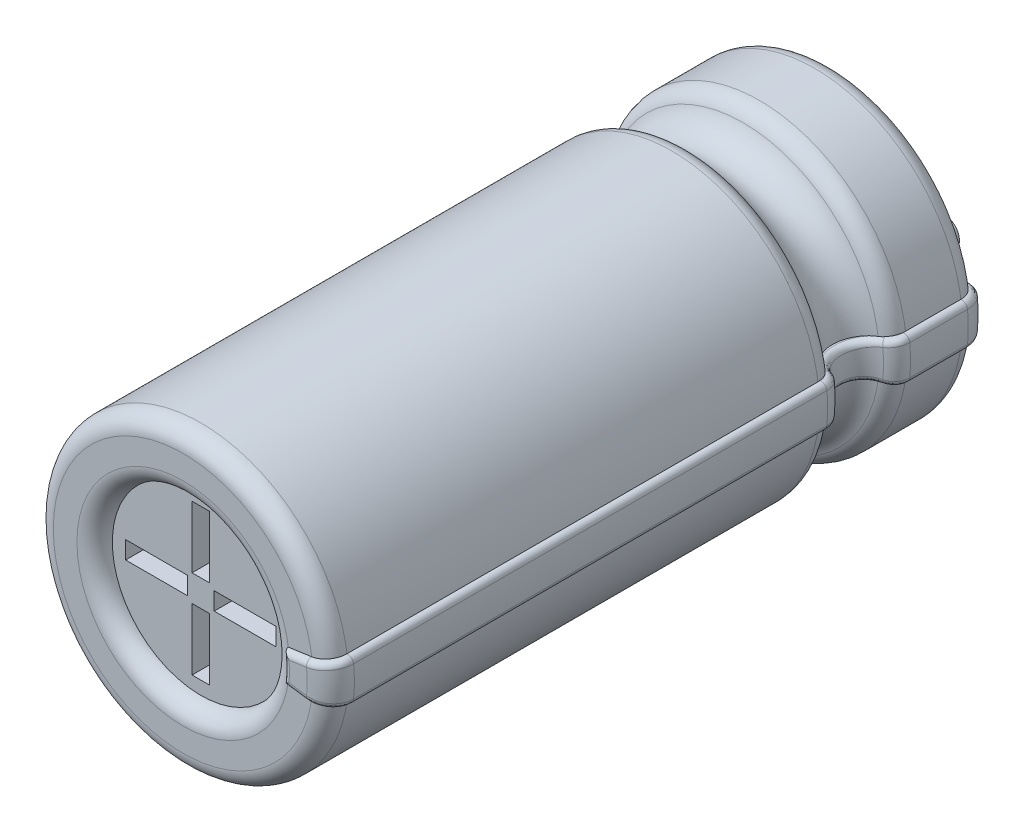
SolidWorks part; units mm, degrees
ref_plane "Спереди" through (0, 0, 0) normal (0, 0, 1) x (1, 0, 0)
ref_plane "Сверху" through (0, 0, 0) normal (0, 1, 0) x (1, 0, 0)
ref_plane "Справа" through (0, 0, 0) normal (1, 0, 0) x (0, 0, -1)
sketch "Эскиз2" plane through (0, 0, 0) normal (0, 0, 1) x (1, 0, 0)
  line L0 (-1, 0) -> (0, 0) construction
  line L1 (0, 0) -> (1, 0) construction
  line L2 (0, -0.75) -> (0, 0.75) construction
  line L3 (0.75, 0) -> (-0.75, 0) construction
  circle A0 centre (0, 0) radius 2.5 construction
  circle A1 centre (0, 0) radius 1.5 construction
  circle A2 centre (-1, 0) radius 0.25 construction
  circle A3 centre (1, 0) radius 0.25 construction
  point P10 (0, 0)
  point P13 (0, 0)
  point P14 (2.5, 0)
  dimension "Диаметр" = 5
  dimension "Диаметр вверху" = 3
  dimension "Диаметр контакта" = 0.5
  dimension "Расстояние между контактами" = 2
  dimension "Расстояние между центрами креста" = 1.5
sketch "Эскиз3" plane through (0, 0, 0) normal (0, 1, 0) x (1, 0, 0)
  line L0 (0, 0) -> (0, -0.1) construction
  line L1 (0, -0.1) -> (0, -2.08) construction
  line L2 (0, -2.08) -> (0, -11.1) construction
  line L3 (0, -11.1) -> (0, -10.8) construction
  line L4 (0, 0) -> (0, 0.8) construction
  line L5 (0, -0.1) -> (0, -0.4) construction
  line L6 (0, -10.8) -> (0, -10.5) construction
  dimension "Высота над поверхностью" = 0.1
  dimension "Высота до выреза" = 1.98
  dimension "Высота" = 11
  dimension "Толщина выреза вверху" = 0.3
  dimension "Длинна контакта" = 0.8
  dimension "Толщина выреза внизу" = 0.3
  dimension "Глубина выреза креста" = 0.3
ref_plane "Плоскость1" through (0, 0, 0.1) normal (0, 0, 1) x (1, 0, 0)
sketch "Эскиз4" plane through (0, 0, 0.1) normal (0, 0, 1) x (1, 0, 0)
  circle A0 centre (0, 0) radius 2.5
  circle A1 centre (0, 0) radius 2.5 construction
extrude "Бобышка-Вытянуть1" add sketch "Эскиз4" along normal up to vertex (11 mm away) up to point (0, 0, 11.1)
sketch "Эскиз5" plane through (0, 0, 11.1) normal (0, 0, 1) x (1, 0, 0)
  circle A0 centre (0, 0) radius 1.5
  circle A1 centre (0, 0) radius 1.5 construction
extrude "Вырез-Вытянуть1" cut sketch "Эскиз5" against normal up to vertex (0.3 mm away) up to point (0, 0, 10.8)
sketch "Эскиз7" plane through (0, 0, 0) normal (0, 1, 0) x (1, 0, 0)
  line L0 (0, -2.08) -> (-2.5, -2.08) construction
  line L1 (-2.5, -0.1) -> (-2.5, -11.1) construction
  circle A0 centre (-2.5, -2.08) radius 0.5
  dimension "Диаметр выреза" = 1
revolve "Повернуть1" add sketch "Эскиз7" angle 360 about L2
combine bodies "Соединить1" operation type subtract main body 104 bodies to subtract 105
sketch "Эскиз8" plane through (0, 0, 0.1) normal (0, 0, -1) x (-1, 0, 0)
  circle A0 centre (0, 0) radius 1.275
  dimension "Диаметр выреза внизу" = 2.55
extrude "Вырез-Вытянуть2" cut sketch "Эскиз8" against normal up to vertex (0.3 mm away) up to point (0, 0, 0.4)
fillet "Скругление3" radius 0.3 6 edges at (2.5, 0, 11.1) (1.5, 0, 11.1) (-2.5, 0, 2.58) (2.5, 0, 1.58) (2.5, 0, 0.1) (-1.275, 0, 0.1)
sketch "Эскиз9" plane through (0, 0, 0.4) normal (0, 0, -1) x (-1, 0, 0)
  circle A0 centre (-1, 0) radius 0.25
  circle A1 centre (1, 0) radius 0.25
  circle A2 centre (1, 0) radius 0.25 construction
  circle A3 centre (-1, 0) radius 0.25 construction
extrude "Бобышка-Вытянуть2" add sketch "Эскиз9" along normal up to vertex (1.2 mm away) separate body up to point (0, 0, -0.8)
sketch "Эскиз10" plane through (0, 0, 10.8) normal (0, 0, 1) x (1, 0, 0)
  line L1 (0.225, 0.15) -> (1.275, 0.15)
  line L2 (0.225, 0.15) -> (0.225, -0.15)
  line L3 (0.225, -0.15) -> (1.275, -0.15)
  line L4 (1.275, 0.15) -> (1.275, -0.15)
  line L5 (0.225, 0.15) -> (1.275, -0.15) construction
  line L6 (0.225, -0.15) -> (1.275, 0.15) construction
  line L7 (-0.225, 0.15) -> (-1.275, 0.15)
  line L8 (-0.225, 0.15) -> (-0.225, -0.15)
  line L9 (-0.225, -0.15) -> (-1.275, -0.15)
  line L10 (-1.275, 0.15) -> (-1.275, -0.15)
  line L11 (-0.225, 0.15) -> (-1.275, -0.15) construction
  line L12 (-0.225, -0.15) -> (-1.275, 0.15) construction
  line L13 (0.15, -1.275) -> (-0.15, -1.275)
  line L14 (0.15, -1.275) -> (0.15, -0.225)
  line L15 (0.15, -0.225) -> (-0.15, -0.225)
  line L16 (-0.15, -1.275) -> (-0.15, -0.225)
  line L17 (0.15, -1.275) -> (-0.15, -0.225) construction
  line L18 (0.15, -0.225) -> (-0.15, -1.275) construction
  line L19 (0.15, 0.225) -> (-0.15, 0.225)
  line L20 (0.15, 0.225) -> (0.15, 1.275)
  line L21 (0.15, 1.275) -> (-0.15, 1.275)
  line L22 (-0.15, 0.225) -> (-0.15, 1.275)
  line L23 (0.15, 0.225) -> (-0.15, 1.275) construction
  line L24 (0.15, 1.275) -> (-0.15, 0.225) construction
  point P0 (0.75, 0)
  point P6 (-0.75, 0)
  point P12 (0, -0.75)
  point P18 (0, 0.75)
  dimension "Ширина выреза креста" = 0.3
  dimension "Длинна выреза креста" = 1.05
extrude "Вырез-Вытянуть3" cut sketch "Эскиз10" against normal up to vertex (0.3 mm away) up to point (0, 0, 10.5)
sketch "Эскиз13" plane through (0, 0, 0) normal (0, 0, 1) x (1, 0, 0)
  circle A0 centre (0, 0) radius 1.575 construction
  circle A1 centre (0, 0) radius 1.575 construction
  circle A2 centre (0, 0) radius 1.8 construction
  circle A3 centre (0, 0) radius 1.8 construction
  point P8 (1.575, 0)
  point P9 (1.8, 0)
sketch "Эскиз12" plane through (0, 0, 0) normal (0, 1, 0) x (1, 0, 0)
  line L1 (1.575, -0.1) -> (1.575, 0) construction
  line L3 (1.8, 0) -> (1.8, -11.1) construction
  line L4 (1.8, -11.1) -> (1.8, -11.2) construction
  line L6 (2.5, 0) -> (2.5, -11.2) construction
  line L8 (2.5, -10.8) -> (2.6, -10.8) construction
  line L14 (2.5, -10.8) -> (-2.5, -10.8) construction
  line L17 (1.575, 0) -> (1.8, -11.1)
  line L18 (1.8, -11.1) -> (1.8, -11.2)
  line L19 (2.2, -11.1) -> (2.2, -11.2) construction
  line L20 (1.8, -11.2) -> (2.2, -11.2)
  line L22 (2.2, -0.1) -> (2.2, 0) construction
  line L23 (1.575, 0) -> (2.2, 0)
  line L24 (2.6, -0.4) -> (2.5, -0.4) construction
  line L25 (2.5, -0.4) -> (-2.5, -0.4) construction
  line L27 (2, -2.08) -> (2.1, -2.08) construction
  line L29 (2.3125, -2.5435) -> (2.3125, -1.6165) construction
  line L30 (2.3125, -2.5435) -> (2.6, -2.5435) construction
  line L32 (-2.3125, -2.5435) -> (2.3125, -2.5435) construction
  line L33 (2.3125, -1.6165) -> (2.6, -1.6165) construction
  line L35 (2.3125, -1.6165) -> (-2.3125, -1.6165) construction
  line L36 (2.6, -1.3779) -> (2.6, -0.4)
  line L37 (2.6, -2.7821) -> (2.6, -10.8)
  arc A0 (2.2, -11.2) -> (2.6, -10.8) centre (2.2, -10.8) ccw
  arc A3 (2.2, 0) -> (2.6, -0.4) centre (2.2, -0.4) cw
  arc A8 (2.3125, -1.6165) -> (2.3125, -2.5435) centre (2.5, -2.08) ccw construction
  arc A9 (2.4179, -2.5062) -> (2.4179, -1.6538) centre (2.6, -2.08) cw
  arc A10 (2.6, -1.3779) -> (2.4179, -1.6538) centre (2.3, -1.3779) cw
  arc A11 (2.6, -2.7821) -> (2.4179, -2.5062) centre (2.3, -2.7821) ccw
  point P24 (2.3125, -2.08)
  dimension "D1" = 0.3
  dimension "Толщина краски" = 0.1
revolve "Повернуть2" add sketch "Эскиз12" angle 8 about L2
fillet "Скругление4" radius 0.1 20 edges at (1.8691, -0.2627, 0) (2.4587, -0.3455, 0.1172) (2.5747, -0.3619, 0.8889) (2.5255, -0.3549, 1.5432) (2.1157, -0.2973, 2.08) (2.5255, -0.3549, 2.6168) (2.5747, -0.3619, 6.7911) (2.4587, -0.3455, 11.0828) (1.8691, 0.2627, 0) (2.4587, 0.3455, 0.1172) (2.5747, 0.3619, 0.8889) (2.5255, 0.3549, 1.5432) (2.1157, 0.2973, 2.08) (2.5255, 0.3549, 2.6168) (2.5747, 0.3619, 6.7911) (2.4587, 0.3455, 11.0828) (1.575, 0, 0) (1.9805, -0.2783, 11.2) (1.9805, 0.2783, 11.2) (1.8, 0, 11.2)
